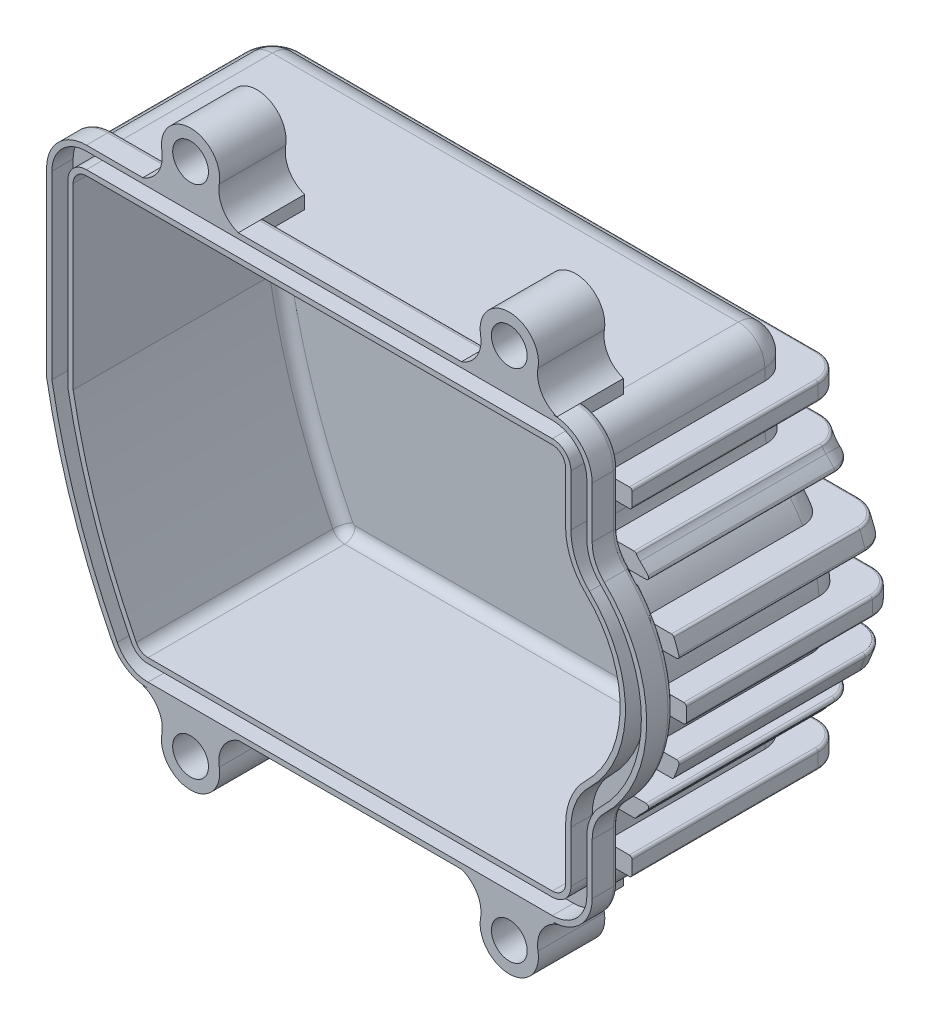
SolidWorks part; units mm, degrees
ref_plane "Front Plane" through (0, 0, 0) normal (0, 0, 1) x (1, 0, 0)
ref_plane "Top Plane" through (0, 0, 0) normal (0, 1, 0) x (1, 0, 0)
ref_plane "Right Plane" through (0, 0, 0) normal (1, 0, 0) x (0, 0, -1)
sketch "Sketch1" plane through (0, 0, 0) normal (0, 0, 1) x (1, 0, 0)
  line L0 (0, 0) -> (97.7064, 0) construction
  line L1 (-64.4985, -77.758) -> (87.7064, -77.758)
  line L2 (-97.7064, 0) -> (-97.7064, 67.758)
  line L3 (-87.7064, 77.758) -> (87.7064, 77.758)
  line L4 (97.7064, -67.758) -> (97.7064, -48.4727)
  line L5 (-97.7064, -77.758) -> (97.7064, 77.758) construction
  line L6 (-97.7064, 77.758) -> (97.7064, -77.758) construction
  line L7 (97.7064, 48.4727) -> (97.7064, 67.758)
  arc A0 (-97.7064, 0) -> (-73.4217, -72.2721) centre (163.3398, 47.5) ccw
  arc A2 (103.7879, -34.1104) -> (103.7879, 34.1104) centre (70.7314, 0) ccw
  arc A3 (-73.4217, -72.2721) -> (-64.4985, -77.758) centre (-64.4985, -67.758) ccw
  arc A4 (87.7064, -77.758) -> (97.7064, -67.758) centre (87.7064, -67.758) ccw
  arc A5 (87.7064, 77.758) -> (97.7064, 67.758) centre (87.7064, 67.758) cw
  arc A6 (-97.7064, 67.758) -> (-87.7064, 77.758) centre (-87.7064, 67.758) cw
  arc A7 (97.7064, 48.4727) -> (103.7879, 34.1104) centre (117.7064, 48.4727) ccw
  arc A8 (103.7879, -34.1104) -> (97.7064, -48.4727) centre (117.7064, -48.4727) ccw
  point P0 (0, 0)
  point P28 (97.7064, 39.0973)
  dimension "D1" = 10
  dimension "D2" = 20
extrude "Boss-Extrude1" add sketch "Sketch1" along normal blind 80
sketch "Sketch2" plane through (0, 0, 80) normal (0, 0, 1) x (1, 0, 0)
  line L0 (87.7064, 72.758) -> (-87.7064, 72.758)
  line L1 (-92.7064, 67.758) -> (-92.7064, 0.4534)
  line L2 (-64.4985, -72.758) -> (87.7064, -72.758)
  line L3 (92.7064, -67.758) -> (92.7064, -48.4727)
  line L4 (92.7064, 48.4727) -> (92.7064, 67.758)
  arc A0 (-87.7064, 72.758) -> (-92.7064, 67.758) centre (-87.7064, 67.758) ccw
  arc A1 (-92.7064, 0.4534) -> (-68.9601, -70.015) centre (163.3398, 47.5) ccw
  arc A2 (-68.9601, -70.015) -> (-64.4985, -72.758) centre (-64.4985, -67.758) ccw
  arc A3 (87.7064, -72.758) -> (92.7064, -67.758) centre (87.7064, -67.758) ccw
  arc A4 (100.3083, -30.5198) -> (92.7064, -48.4727) centre (117.7064, -48.4727) ccw
  arc A5 (100.3083, -30.5198) -> (100.3083, 30.5198) centre (70.7314, 0) ccw
  arc A6 (92.7064, 48.4727) -> (100.3083, 30.5198) centre (117.7064, 48.4727) ccw
  arc A7 (92.7064, 67.758) -> (87.7064, 72.758) centre (87.7064, 67.758) ccw
extrude "Cut-Extrude1" cut sketch "Sketch2" against normal blind 75
ref_plane "Plane1" through (0, 0, 70) normal (0, 0, 1) x (1, 0, 0)
sketch "Sketch3" plane through (0, 0, 70) normal (0, 0, 1) x (1, 0, 0)
  line L0 (87.7064, 82.758) -> (-87.7064, 82.758)
  line L1 (-102.7064, 67.758) -> (-102.7064, -0.4491)
  line L2 (-64.4985, -82.758) -> (87.7064, -82.758)
  line L3 (102.7064, -67.758) -> (102.7064, -48.4727)
  line L4 (102.7064, 48.4727) -> (102.7064, 67.758)
  line L6 (87.7064, 72.758) -> (-87.7064, 72.758) construction
  line L7 (87.7064, 72.758) -> (-87.7064, 72.758)
  line L8 (92.7064, 48.4727) -> (92.7064, 67.758) construction
  line L9 (92.7064, -67.758) -> (92.7064, -48.4727) construction
  line L21 (-64.4985, -72.758) -> (87.7064, -72.758) construction
  line L22 (-92.7064, 67.758) -> (-92.7064, 0.4534) construction
  line L23 (92.7064, 48.4727) -> (92.7064, 67.758)
  line L24 (92.7064, -67.758) -> (92.7064, -48.4727)
  line L25 (-64.4985, -72.758) -> (87.7064, -72.758)
  line L31 (-92.7064, 67.758) -> (-92.7064, 0.4534)
  arc A0 (-87.7064, 82.758) -> (-102.7064, 67.758) centre (-87.7064, 67.758) ccw
  arc A1 (-102.7064, -0.4491) -> (-77.8833, -74.5291) centre (163.3398, 47.5) ccw
  arc A2 (-77.8833, -74.5291) -> (-64.4985, -82.758) centre (-64.4985, -67.758) ccw
  arc A3 (87.7064, -82.758) -> (102.7064, -67.758) centre (87.7064, -67.758) ccw
  arc A4 (107.2675, -37.701) -> (102.7064, -48.4727) centre (117.7064, -48.4727) ccw
  arc A5 (107.2675, -37.701) -> (107.2675, 37.701) centre (70.7314, 0) ccw
  arc A6 (102.7064, 48.4727) -> (107.2675, 37.701) centre (117.7064, 48.4727) ccw
  arc A7 (102.7064, 67.758) -> (87.7064, 82.758) centre (87.7064, 67.758) ccw
  arc A9 (92.7064, 48.4727) -> (100.3083, 30.5198) centre (117.7064, 48.4727) ccw construction
  arc A10 (92.7064, 67.758) -> (87.7064, 72.758) centre (87.7064, 67.758) ccw construction
  arc A11 (100.3083, -30.5198) -> (100.3083, 30.5198) centre (70.7314, 0) ccw construction
  arc A12 (100.3083, -30.5198) -> (92.7064, -48.4727) centre (117.7064, -48.4727) ccw construction
  arc A13 (87.7064, -72.758) -> (92.7064, -67.758) centre (87.7064, -67.758) ccw construction
  arc A14 (-68.9601, -70.015) -> (-64.4985, -72.758) centre (-64.4985, -67.758) ccw construction
  arc A15 (-92.7064, 0.4534) -> (-68.9601, -70.015) centre (163.3398, 47.5) ccw construction
  arc A32 (-87.7064, 72.758) -> (-92.7064, 67.758) centre (-87.7064, 67.758) ccw construction
  arc A33 (92.7064, 48.4727) -> (100.3083, 30.5198) centre (117.7064, 48.4727) ccw
  arc A34 (92.7064, 67.758) -> (87.7064, 72.758) centre (87.7064, 67.758) ccw
  arc A35 (100.3083, -30.5198) -> (100.3083, 30.5198) centre (70.7314, 0) ccw
  arc A36 (100.3083, -30.5198) -> (92.7064, -48.4727) centre (117.7064, -48.4727) ccw
  arc A37 (87.7064, -72.758) -> (92.7064, -67.758) centre (87.7064, -67.758) ccw
  arc A47 (-68.9601, -70.015) -> (-64.4985, -72.758) centre (-64.4985, -67.758) ccw
  arc A48 (-92.7064, 0.4534) -> (-68.9601, -70.015) centre (163.3398, 47.5) ccw
  arc A49 (-87.7064, 72.758) -> (-92.7064, 67.758) centre (-87.7064, 67.758) ccw
extrude "Boss-Extrude3" add sketch "Sketch3" along normal blind 10
fillet "Fillet2" radius 2 13 edges at (-92.9852, -38.3906, 70) (-72.3546, -80.5362, 70) (11.6039, -82.758, 70) (98.313, -78.3646, 70) (102.7064, -58.1154, 70) (103.8937, -42.6239, 70) (-102.7064, 33.6545, 70) (-98.313, 78.3646, 70) (0, 82.758, 70) (98.313, 78.3646, 70) (102.7064, 58.1154, 70) (103.8937, 42.6239, 70) (123.2314, 0, 70)
sketch "Sketch4" plane through (0, 0, 80) normal (0, 0, 1) x (1, 0, 0)
  line L0 (87.7064, 80.758) -> (-87.7064, 80.758)
  line L1 (-100.7064, 67.758) -> (-100.7064, -0.27)
  line L2 (-64.4985, -80.758) -> (87.7064, -80.758)
  line L3 (100.7064, -67.758) -> (100.7064, -48.4727)
  line L4 (100.7064, 48.4727) -> (100.7064, 67.758)
  line L26 (-64.4985, -74.758) -> (87.7064, -74.758)
  line L27 (94.7064, -67.758) -> (94.7064, -48.4727)
  line L28 (94.7064, 48.4727) -> (94.7064, 67.758)
  line L29 (-94.7064, 67.758) -> (-94.7064, 0.2715)
  line L30 (87.7064, 74.758) -> (-87.7064, 74.758)
  line L31 (-64.4985, -74.758) -> (87.7064, -74.758)
  line L32 (94.7064, -67.758) -> (94.7064, -48.4727)
  line L33 (94.7064, 48.4727) -> (94.7064, 67.758)
  line L34 (-94.7064, 67.758) -> (-94.7064, 0.2715)
  line L35 (87.7064, 74.758) -> (-87.7064, 74.758)
  arc A0 (-87.7064, 80.758) -> (-100.7064, 67.758) centre (-87.7064, 67.758) ccw
  arc A1 (-100.7064, -0.27) -> (-76.0987, -73.6263) centre (163.3398, 47.5) ccw
  arc A2 (-76.0987, -73.6263) -> (-64.4985, -80.758) centre (-64.4985, -67.758) ccw
  arc A3 (87.7064, -80.758) -> (100.7064, -67.758) centre (87.7064, -67.758) ccw
  arc A4 (105.8757, -36.2648) -> (100.7064, -48.4727) centre (117.7064, -48.4727) ccw
  arc A5 (105.8757, -36.2648) -> (105.8757, 36.2648) centre (70.7314, 0) ccw
  arc A6 (100.7064, 48.4727) -> (105.8757, 36.2648) centre (117.7064, 48.4727) ccw
  arc A7 (100.7064, 67.758) -> (87.7064, 80.758) centre (87.7064, 67.758) ccw
  arc A36 (-70.7448, -70.9178) -> (-64.4985, -74.758) centre (-64.4985, -67.758) ccw
  arc A37 (87.7064, -74.758) -> (94.7064, -67.758) centre (87.7064, -67.758) ccw
  arc A38 (101.7001, -31.9561) -> (94.7064, -48.4727) centre (117.7064, -48.4727) ccw
  arc A39 (94.7064, 48.4727) -> (101.7001, 31.9561) centre (117.7064, 48.4727) ccw
  arc A40 (101.7001, -31.9561) -> (101.7001, 31.9561) centre (70.7314, 0) ccw
  arc A41 (94.7064, 67.758) -> (87.7064, 74.758) centre (87.7064, 67.758) ccw
  arc A42 (-94.7064, 0.2715) -> (-70.7448, -70.9178) centre (163.3398, 47.5) ccw
  arc A43 (-87.7064, 74.758) -> (-94.7064, 67.758) centre (-87.7064, 67.758) ccw
  arc A44 (-70.7448, -70.9178) -> (-64.4985, -74.758) centre (-64.4985, -67.758) ccw
  arc A45 (87.7064, -74.758) -> (94.7064, -67.758) centre (87.7064, -67.758) ccw
  arc A46 (101.7001, -31.9561) -> (94.7064, -48.4727) centre (117.7064, -48.4727) ccw
  arc A47 (94.7064, 48.4727) -> (101.7001, 31.9561) centre (117.7064, 48.4727) ccw
  arc A48 (101.7001, -31.9561) -> (101.7001, 31.9561) centre (70.7314, 0) ccw
  arc A49 (94.7064, 67.758) -> (87.7064, 74.758) centre (87.7064, 67.758) ccw
  arc A50 (-94.7064, 0.2715) -> (-70.7448, -70.9178) centre (163.3398, 47.5) ccw
  arc A51 (-87.7064, 74.758) -> (-94.7064, 67.758) centre (-87.7064, 67.758) ccw
  dimension "D2" = 2
  dimension "D3" = 6
extrude "Cut-Extrude2" cut sketch "Sketch4" against normal blind 8
fillet "Fillet3" radius 10 13 edges at (-88.1735, -37.0128, 0) (-69.7359, -76.2768, 0) (11.6039, -77.758, 0) (94.7775, -74.8291, 0) (97.7064, -58.1154, 0) (99.2894, -40.6743, 0) (118.2314, 0, 0) (99.2894, 40.6743, 0) (97.7064, 58.1154, 0) (94.7775, 74.8291, 0) (-97.7064, 33.879, 0) (-94.7775, 74.8291, 0) (0, 77.758, 0)
sketch "Sketch5" plane through (0, 0, 0) normal (0, 1, 0) x (1, 0, 0)
  line L10 (-107.7064, -70) -> (-107.7064, -10)
  line L11 (-87.7064, 10) -> (87.7064, 10)
  line L12 (96.8287, 10) -> (87.7064, 10)
  line L13 (108.2314, 10) -> (96.8287, 10)
  line L14 (128.2314, -70) -> (128.2314, -10)
  line L15 (-107.7064, -70) -> (-97.7064, -70)
  line L16 (118.2314, -70) -> (128.2314, -70)
  line L17 (-97.7064, -70) -> (118.2314, -70)
  line L18 (108.2314, 10) -> (128.2314, 10)
  line L19 (128.2314, 10) -> (128.2314, -10)
  line L20 (-87.7064, 10) -> (-107.7064, 10)
  line L21 (-107.7064, 10) -> (-107.7064, -10)
extrude "Boss-Extrude8" add sketch "Sketch5" along normal mid plane 7
pattern_linear "LPattern5" count 4 spacing 20 along (0, 1, 0) count 4 spacing 20 along (0, -1, 0) of "Boss-Extrude8"
sketch "Sketch6" plane through (0, 0, 0) normal (0, 0, -1) x (-1, 0, 0)
  line L10 (87.7064, 87.758) -> (-87.7064, 87.758)
  line L11 (-107.7064, 48.4727) -> (-107.7064, 67.758)
  line L12 (107.7064, -0.894) -> (107.7064, 67.758)
  line L13 (64.4985, -87.758) -> (-87.7064, -87.758)
  line L14 (-107.7064, -67.758) -> (-107.7064, -48.4727)
  line L16 (-138.382, -94.4882) -> (138.382, -94.4882)
  line L17 (-138.382, -94.4882) -> (-138.382, 94.4882)
  line L18 (-138.382, 94.4882) -> (138.382, 94.4882)
  line L19 (138.382, -94.4882) -> (138.382, 94.4882)
  line L20 (-138.382, -94.4882) -> (138.382, 94.4882) construction
  line L21 (-138.382, 94.4882) -> (138.382, -94.4882) construction
  arc A16 (-87.7064, 87.758) -> (-107.7064, 67.758) centre (-87.7064, 67.758) ccw
  arc A17 (-110.7472, 41.2916) -> (-107.7064, 48.4727) centre (-117.7064, 48.4727) ccw
  arc A18 (-110.7472, 41.2916) -> (-110.7472, -41.2916) centre (-70.7314, 0) ccw
  arc A19 (107.7064, 67.758) -> (87.7064, 87.758) centre (87.7064, 67.758) ccw
  arc A20 (82.3449, -76.7861) -> (107.7064, -0.894) centre (-163.3398, 47.5) ccw
  arc A21 (64.4985, -87.758) -> (82.3449, -76.7861) centre (64.4985, -67.758) ccw
  arc A22 (-107.7064, -67.758) -> (-87.7064, -87.758) centre (-87.7064, -67.758) ccw
  arc A23 (-107.7064, -48.4727) -> (-110.7472, -41.2916) centre (-117.7064, -48.4727) ccw
  point P0 (0, 0)
extrude "Cut-Extrude4" cut sketch "Sketch6" against normal mid plane 140
fillet "Fillet4" radius 10 17 edges at (109.8112, 42.3355, -10) (109.8112, -42.3355, -10) (-107.7064, 60, -10) (-107.7064, 40, -10) (-107.7064, 20, -10) (-107.4704, -2.1976, -10) (-107.7064, 1.303, -10) (-103.589, -20.0058, -10) (-97.7165, -40.0079, -10) (-90.1352, -60.0102, -10) (107.7064, 60, -10) (113.0221, 38.9583, -10) (124.6254, 20.0423, -10) (128.2314, 0, -10) (124.6254, -20.0423, -10) (113.0221, -38.9583, -10) (107.7064, -60, -10)
fillet "Fillet5" radius 1 72 edges at (107.7064, 63.5, 35) (104.7775, 63.5, -7.0711) (-107.7064, 63.5, 35) (-104.7775, 63.5, -7.0711) (107.7064, 56.5, 35) (104.7775, 56.5, -7.0711) (-107.7064, 56.5, 35) (-104.7775, 56.5, -7.0711) (115.1612, 36.5, 35) (113.3083, 36.5, -5.1354) (-107.7064, 36.5, 35) (-104.7775, 36.5, -7.0711) (109.0305, 43.5, 35) (106.9696, 43.5, -5.7699) (-107.7064, 43.5, 35) (-104.7775, 43.5, -7.0711) (123.21, 23.5, 35) (121.1568, 23.5, -5.8193) (-107.7064, 23.5, 35) (-104.7775, 23.5, -7.0711) (125.8132, 16.5, 35) (122.1727, 16.5, -7.5799) (-107.7064, 16.5, 35) (-104.7775, 16.5, -7.0711) (128.1248, 3.5, 35) (125.9366, 3.5, -6.2378) (-107.7064, 3.5, 35) (-104.7775, 3.5, -7.0711) (128.1248, -3.5, 35) (124.3752, -3.5, -7.8) (-107.2282, -3.5, 35) (-105.0641, -3.5, -6.1649) (125.8132, -16.5, 35) (123.6901, -16.5, -6.0404) (-104.4512, -16.5, 35) (-100.7363, -16.5, -7.6935) (123.21, -23.5, 35) (119.792, -23.5, -7.2396) (-102.6809, -23.5, 35) (-100.5422, -23.5, -6.0868) (109.0305, -43.5, 35) (105.1463, -43.5, -7.6068) (-96.5198, -43.5, 35) (-94.4147, -43.5, -5.9813) (115.1612, -36.5, 35) (113.3083, -36.5, -5.1354) (-98.8663, -36.5, 35) (-95.1909, -36.5, -7.5975) (107.7064, -56.5, 35) (104.7775, -56.5, -7.0711) (-91.5955, -56.5, 35) (-87.9879, -56.5, -7.4568) (107.7064, -63.5, 35) (104.7775, -63.5, -7.0711) (-88.6265, -63.5, 35) (-86.5629, -63.5, -5.8466) (0, 63.5, -10) (0, 56.5, -10) (1.9898, 36.5, -10) (0.314, 43.5, -10) (7.1523, 23.5, -10) (8.7836, 16.5, -10) (10.198, 3.5, -10) (10.5285, -3.5, -10) (10.5575, -16.5, -10) (9.847, -23.5, -10) (6.2173, -43.5, -10) (6.6703, -36.5, -10) (8.4725, -56.5, -10) (10.0238, -63.5, -10)
sketch "Sketch7" plane through (0, 0, 72) normal (0, 0, 1) x (1, 0, 0)
  line L0 (-92.7064, 67.758) -> (-92.7064, 0.4534) construction
  line L1 (-64.4985, -72.758) -> (87.7064, -72.758) construction
  line L2 (92.7064, -67.758) -> (92.7064, -48.4727) construction
  line L3 (92.7064, 48.4727) -> (92.7064, 67.758) construction
  line L4 (87.7064, 72.758) -> (-87.7064, 72.758) construction
  line L5 (87.7064, 72.758) -> (-87.7064, 72.758)
  line L6 (92.7064, 48.4727) -> (92.7064, 67.758)
  line L7 (92.7064, -67.758) -> (92.7064, -48.4727)
  line L8 (-64.4985, -72.758) -> (87.7064, -72.758)
  line L9 (-92.7064, 67.758) -> (-92.7064, 0.4534)
  arc A1 (100.3083, -30.5198) -> (100.3083, 30.5198) centre (70.7314, 0) ccw construction
  arc A2 (-87.7064, 72.758) -> (-92.7064, 67.758) centre (-87.7064, 67.758) ccw construction
  arc A3 (-92.7064, 0.4534) -> (-68.9601, -70.015) centre (163.3398, 47.5) ccw construction
  arc A4 (-68.9601, -70.015) -> (-64.4985, -72.758) centre (-64.4985, -67.758) ccw construction
  arc A5 (87.7064, -72.758) -> (92.7064, -67.758) centre (87.7064, -67.758) ccw construction
  arc A6 (100.3083, -30.5198) -> (92.7064, -48.4727) centre (117.7064, -48.4727) ccw construction
  arc A7 (92.7064, 48.4727) -> (100.3083, 30.5198) centre (117.7064, 48.4727) ccw construction
  arc A8 (92.7064, 67.758) -> (87.7064, 72.758) centre (87.7064, 67.758) ccw construction
  arc A9 (92.7064, 67.758) -> (87.7064, 72.758) centre (87.7064, 67.758) ccw
  arc A10 (92.7064, 48.4727) -> (100.3083, 30.5198) centre (117.7064, 48.4727) ccw
  arc A11 (100.3083, -30.5198) -> (100.3083, 30.5198) centre (70.7314, 0) ccw
  arc A12 (100.3083, -30.5198) -> (92.7064, -48.4727) centre (117.7064, -48.4727) ccw
  arc A13 (87.7064, -72.758) -> (92.7064, -67.758) centre (87.7064, -67.758) ccw
  arc A14 (-68.9601, -70.015) -> (-64.4985, -72.758) centre (-64.4985, -67.758) ccw
  arc A15 (-92.7064, 0.4534) -> (-68.9601, -70.015) centre (163.3398, 47.5) ccw
  arc A16 (-87.7064, 72.758) -> (-92.7064, 67.758) centre (-87.7064, 67.758) ccw
extrude "Cut-Extrude5" cut sketch "Sketch7" against normal blind 70
sketch "Sketch8" plane through (0, 0, 80) normal (0, 0, 1) x (1, 0, 0)
  line L0 (-64.4985, -82.758) -> (87.7064, -82.758) construction
  line L1 (-48.5016, -96.9592) -> (-48.5016, -131.3296) construction
  line L2 (11.4984, -0.0562) -> (11.4984, -182.9602) construction
  line L3 (-66.4646, -82.758) -> (-30.5386, -82.758)
  line L4 (53.5354, -82.758) -> (89.4614, -82.758)
  arc A0 (-59.3087, -95.07) -> (-37.6945, -95.07) centre (-48.5016, -96.9592) ccw
  circle A1 centre (-48.5016, -96.9592) radius 6.7329
  arc A2 (-37.6945, -95.07) -> (-30.5386, -82.758) centre (-26.8013, -93.1658) cw
  arc A3 (-59.3087, -95.07) -> (-66.4646, -82.758) centre (-70.2019, -93.1658) ccw
  arc A4 (82.3055, -95.07) -> (89.4614, -82.758) centre (93.1987, -93.1658) cw
  arc A5 (60.6913, -95.07) -> (53.5354, -82.758) centre (49.7981, -93.1658) ccw
  circle A6 centre (71.4984, -96.9592) radius 6.7329
  arc A7 (82.3055, -95.07) -> (60.6913, -95.07) centre (71.4984, -96.9592) cw
  dimension "D1" = 60
extrude "Boss-Extrude9" add sketch "Sketch8" against normal blind 25
sketch "Sketch11" plane through (0, 0, 55) normal (0, 0, -1) x (-1, 0, 0)
  line L0 (-89.4614, -82.758) -> (-89.4614, -77.6028)
  line L1 (-89.4614, -77.6028) -> (-53.5812, -77.758)
  line L2 (64.4985, -77.758) -> (-87.7064, -77.758) construction
  line L3 (-53.5812, -77.758) -> (-53.5354, -82.758)
  line L4 (-53.5354, -82.758) -> (-89.4614, -82.758)
  line L5 (-11.4984, -182.9602) -> (-11.4984, -0.0562) construction
  line L6 (66.4646, -82.758) -> (66.4646, -77.6028)
  line L7 (66.4646, -77.6028) -> (30.5844, -77.758)
  line L8 (30.5844, -77.758) -> (30.5386, -82.758)
  line L9 (30.5386, -82.758) -> (66.4646, -82.758)
  arc A0 (-97.7064, -67.758) -> (-87.7064, -77.758) centre (-87.7064, -67.758) ccw construction
extrude "Boss-Extrude10" add sketch "Sketch11" against normal blind 16
mirror "Mirror1" about plane through (0, 0, 0) normal (0, 1, 0) of "Boss-Extrude9"
mirror "Mirror2" about plane through (0, 0, 0) normal (0, 1, 0) of "Boss-Extrude10"
fillet "Fillet6" radius 4 13 edges at (-83.3623, -35.6331, 2) (-67.1172, -72.0174, 2) (11.6039, -72.758, 2) (91.242, -71.2936, 2) (92.7064, -58.1154, 2) (94.6852, -38.7247, 2) (-92.7064, 34.1057, 2) (-91.242, 71.2936, 2) (0, 72.758, 2) (91.242, 71.2936, 2) (92.7064, 58.1154, 2) (94.6852, 38.7247, 2) (113.2314, 0, 2)
